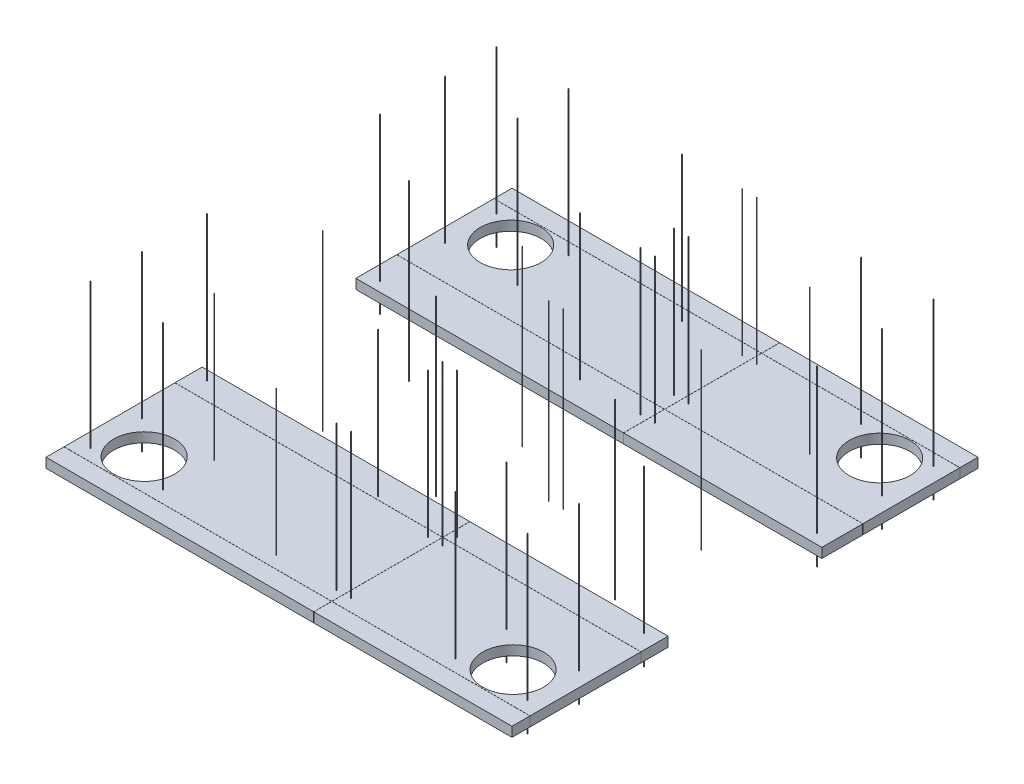
SolidWorks part; units mm, degrees
ref_plane "Front" through (0, 0, 0) normal (0, 0, 1) x (1, 0, 0)
ref_plane "Top" through (0, 0, 0) normal (0, 1, 0) x (1, 0, 0)
ref_plane "Right" through (0, 0, 0) normal (1, 0, 0) x (0, 0, -1)
sketch "Sketch1" plane through (0, 0, 0) normal (0, 1, 0) x (1, 0, 0)
  line L1 (-2454.275, 2454.275) -> (2454.275, 2454.275)
  line L2 (-2454.275, 2454.275) -> (-2454.275, -2454.275)
  line L3 (-2454.275, -2454.275) -> (2454.275, -2454.275)
  line L4 (2454.275, 2454.275) -> (2454.275, -2454.275)
  line L5 (-2454.275, 2454.275) -> (2454.275, -2454.275) construction
  line L6 (-2454.275, -2454.275) -> (2454.275, 2454.275) construction
  point P0 (0, 0)
  dimension "D1" = 4908.55
  dimension "D2" = 4908.55
extrude "Boss-Extrude1" add sketch "Sketch1" along normal blind 101.6
sketch "Sketch2" plane through (0, 101.6, 0) normal (0, 1, 0) x (1, 0, 0)
  line L0 (-2454.275, 2454.275) -> (-2454.275, -2454.275) construction
  line L1 (2454.275, -809.625) -> (-2454.275, -809.625)
  line L2 (2454.275, -809.625) -> (2454.275, 809.625)
  line L3 (2454.275, 809.625) -> (-2454.275, 809.625)
  line L4 (-2454.275, -809.625) -> (-2454.275, 809.625)
  line L5 (2454.275, -809.625) -> (-2454.275, 809.625) construction
  line L6 (2454.275, 809.625) -> (-2454.275, -809.625) construction
  point P0 (0, 0)
  dimension "D1" = 1619.25
extrude "Cut-Extrude1" cut sketch "Sketch2" against normal through all
sketch "Sketch4" plane through (0, 101.6, 0) normal (0, 1, 0) x (1, 0, 0)
  line L0 (-2454.275, -2263.775) -> (2454.275, -2263.775)
  line L3 (-2454.275, -2454.275) -> (2454.275, -2454.275) construction
  line L4 (-2454.275, -1095.375) -> (2454.275, -1095.375)
  line L5 (-2454.275, -809.625) -> (-2454.275, -2454.275) construction
  line L6 (-2454.275, -809.625) -> (2454.275, -809.625) construction
  line L7 (-2454.275, 2263.775) -> (2454.275, 2263.775)
  line L10 (-2454.275, 1241.425) -> (2454.275, 1241.425)
  line L11 (-2454.275, 2454.275) -> (-2454.275, 809.625) construction
  line L12 (2454.275, 809.625) -> (2454.275, 2454.275) construction
  line L13 (2454.275, 2454.275) -> (-2454.275, 2454.275) construction
  line L14 (2454.275, 809.625) -> (-2454.275, 809.625) construction
  line L15 (-2454.275, -1095.375) -> (-2454.275, -2263.775) construction
  line L16 (2454.275, -1095.375) -> (2454.275, -2263.775) construction
  line L17 (2454.275, 1241.425) -> (2454.275, 2263.775) construction
  line L18 (-2454.275, 1241.425) -> (-2454.275, 2263.775) construction
  line L19 (2454.275, -2454.275) -> (2454.275, -809.625) construction
  dimension "D1" = 190.5
  dimension "D2" = 1168.4
  dimension "D3" = 285.75
  dimension "D4" = 190.5
  dimension "D5" = 1022.35
  dimension "D6" = 431.8
extrude "Cut-Extrude-Thin1" cut sketch "Sketch4" against normal through all thin thin type one direction wall 1.27
sketch "Sketch5" plane through (0, 101.6, 0) normal (0, 1, 0) x (1, 0, 0)
  line L0 (365.125, -2454.275) -> (365.125, 2454.275)
  line L1 (-2454.275, -2454.275) -> (2454.275, -2454.275) construction
  line L2 (2454.275, 2454.275) -> (-2454.275, 2454.275) construction
  line L3 (2454.275, -2263.775) -> (2454.275, -1096.645) construction
  line L4 (-2454.275, -1096.645) -> (-2454.275, -2263.775) construction
  dimension "D1" = 2089.15
  dimension "D2" = 2819.4
extrude "Cut-Extrude-Thin2" cut sketch "Sketch5" against normal through all and the other way through all thin thin type one direction wall 1.27
sketch "Sketch8" plane through (0, 101.6, 0) normal (0, 1, 0) x (1, 0, 0)
  line L0 (-974.0807, 502.3386) -> (-974.0807, 1597.0052) construction
sketch "Sketch6" plane through (0, 101.6, 0) normal (0, 1, 0) x (1, 0, 0)
  line L0 (1943.1, 1929.13) -> (1943.1, 2262.505) construction
  line L1 (-1943.1, 1929.13) -> (1943.1, 1929.13) construction
  line L2 (-1943.1, 1929.13) -> (-1943.1, -1931.67) construction
  line L3 (-1943.1, -1931.67) -> (1943.1, -1931.67) construction
  line L4 (1943.1, 1929.13) -> (1943.1, -1931.67) construction
  line L5 (-1943.1, -1931.67) -> (-1943.1, -2265.045) construction
  line L6 (-2454.275, -2265.045) -> (365.125, -2265.045) construction
  line L7 (366.395, 2262.505) -> (2454.275, 2262.505) construction
  line L9 (2454.275, 1241.425) -> (2454.275, 2262.505) construction
  line L11 (-2454.275, -1096.645) -> (-2454.275, -2263.775) construction
  circle A0 centre (1943.1, 1929.13) radius 320.675
  circle A1 centre (-1943.1, 1929.13) radius 320.675
  circle A2 centre (-1943.1, -1931.67) radius 320.675
  circle A3 centre (1943.1, -1931.67) radius 320.675
  dimension "D1" = 641.35
  dimension "D3" = 190.5
  dimension "D4" = 190.5
  dimension "D2" = 12.7
extrude "DUCT HOLES" cut sketch "Sketch6" against normal through all
sketch "Sketch7" plane through (0, 101.6, 0) normal (0, 1, 0) x (1, 0, 0)
  line L0 (-1539.875, 2301.875) -> (-346.075, 2301.875) construction
  line L1 (-1539.875, 2301.875) -> (-2454.275, 2301.875) construction
  line L2 (-2454.275, 2454.275) -> (-2454.275, 2263.775) construction
  line L3 (365.125, 2454.275) -> (-2454.275, 2454.275) construction
  line L4 (-346.075, 2301.875) -> (365.125, 2301.875) construction
  line L5 (365.125, 2263.775) -> (365.125, 2454.275) construction
  line L6 (1539.875, 1597.025) -> (1539.875, 1063.625) construction
  line L7 (365.125, 2301.875) -> (974.725, 2301.875) construction
  line L8 (974.725, 2301.875) -> (1539.875, 2301.875) construction
  line L9 (1539.875, 2301.875) -> (2454.275, 2301.875) construction
  line L10 (2454.275, 2263.775) -> (2454.275, 2454.275) construction
  line L11 (366.395, 2263.775) -> (366.395, 2454.275) construction
  line L12 (2454.275, 1597.025) -> (-2454.275, 1597.025) construction
  line L13 (2454.275, 1241.425) -> (2454.275, 2262.505) construction
  line L14 (-2454.275, 2262.505) -> (-2454.275, 1241.425) construction
  line L15 (1539.875, 2301.875) -> (1539.875, 1597.025) construction
  line L16 (-2454.275, 1241.425) -> (365.125, 1241.425) construction
  line L17 (-346.075, 2301.875) -> (-346.075, 1597.025) construction
  line L18 (974.725, 2301.875) -> (974.725, 1597.025) construction
  line L19 (-2454.275, 2136.775) -> (2454.275, 2136.775) construction
  line L20 (-2454.275, 2263.775) -> (365.125, 2263.775) construction
  line L21 (-1539.875, 2301.875) -> (-1539.875, 2136.775) construction
  line L22 (-2454.275, 1063.625) -> (2454.275, 1063.625) construction
  line L23 (-2454.275, 1240.155) -> (-2454.275, 809.625) construction
  line L24 (2454.275, 809.625) -> (2454.275, 1240.155) construction
  line L25 (365.125, 809.625) -> (-2454.275, 809.625) construction
  line L26 (-1539.875, 1063.625) -> (-1539.875, 1597.025) construction
  line L27 (-346.075, 1597.025) -> (-346.075, 1063.625) construction
  line L28 (-2107.4102, -2022.1425) -> (-2107.4102, -819.4758) construction
  line L29 (-1539.875, 1285.875) -> (1539.875, 1285.875) construction
  line L30 (-2301.875, 1597.025) -> (-2301.875, 1063.625) construction
  line L31 (2301.875, 1597.025) -> (2301.875, 1063.625) construction
  line L32 (-2454.275, 1240.155) -> (365.125, 1240.155) construction
  line L33 (441.325, 1063.625) -> (288.925, 1063.625) construction
  line L34 (441.325, 1063.625) -> (441.325, 1416.685) construction
  line L35 (441.325, 1416.685) -> (288.925, 1416.685) construction
  line L36 (288.925, 1063.625) -> (288.925, 1416.685) construction
  line L37 (-2454.275, 1240.155) -> (365.125, 1240.155) construction
  line L38 (365.125, 809.625) -> (365.125, 1240.155) construction
  line L39 (365.125, 809.625) -> (365.125, 1240.155) construction
  line L40 (440.6472, 1241.425) -> (440.6472, 1063.625) construction
  line L41 (288.925, -1172.845) -> (441.325, -1172.845) construction
  line L42 (288.925, -1172.845) -> (288.925, -1020.445) construction
  line L43 (288.925, -1020.445) -> (441.325, -1020.445) construction
  line L44 (441.325, -1172.845) -> (441.325, -1020.445) construction
  line L45 (366.395, 1241.425) -> (2454.275, 1241.425) construction
  line L46 (1539.875, 1063.625) -> (1539.875, -2454.275) construction
  line L47 (366.395, -2454.275) -> (2454.275, -2454.275) construction
  line L48 (-2454.275, -1096.645) -> (365.125, -1096.645) construction
  line L49 (-2454.275, -1096.645) -> (365.125, -1096.645) construction
  line L50 (-2301.875, 1063.625) -> (-2301.875, 911.225) construction
  line L51 (-2301.875, 911.225) -> (2301.875, 911.225) construction
  line L52 (2301.875, 911.225) -> (2301.875, 1063.625) construction
  line L53 (-1539.875, 1063.625) -> (-1539.875, -2454.275) construction
  line L54 (-2454.275, -2454.275) -> (365.125, -2454.275) construction
  line L55 (1539.875, 454.025) -> (-1539.875, 454.025) construction
  line L56 (288.925, 1063.625) -> (288.925, -2454.275) construction
  line L57 (441.325, 1063.625) -> (441.325, -2454.275) construction
  line L58 (-346.075, 1063.625) -> (-346.075, -2454.275) construction
  line L59 (441.325, 98.425) -> (288.925, 98.425) construction
  line L60 (441.325, 1063.625) -> (441.325, 2301.875) construction
  line L61 (288.925, 1063.625) -> (288.925, 2301.875) construction
  circle A0 centre (-1539.875, 2301.875) radius 3.175 construction
  circle A4 centre (1539.875, 1597.025) radius 3.175
  circle A5 centre (-1539.875, 1597.025) radius 3.175
  circle A6 centre (441.325, 1063.625) radius 3.175
  circle A7 centre (-346.075, 1597.025) radius 3.175 construction
  circle A8 centre (974.725, 1597.025) radius 3.175 construction
  circle A9 centre (-346.075, 2136.775) radius 3.175
  circle A10 centre (-1539.875, 2136.775) radius 3.175
  circle A11 centre (974.725, 2136.775) radius 3.175 construction
  circle A12 centre (1539.875, 2136.775) radius 3.175
  circle A13 centre (-346.075, 1063.625) radius 3.175
  circle A14 centre (-1539.875, 1063.625) radius 3.175 construction
  circle A15 centre (1539.875, 1063.625) radius 3.175 construction
  circle A16 centre (-2301.875, 1597.025) radius 3.175
  circle A17 centre (2301.875, 1597.025) radius 3.175
  circle A18 centre (-2301.875, 2136.775) radius 3.175
  circle A19 centre (2301.875, 2136.775) radius 3.175
  circle A20 centre (219.075, 2301.875) radius 3.175 construction
  circle A21 centre (658.495, 2301.875) radius 3.175 construction
  circle A22 centre (1539.875, 2301.875) radius 3.175 construction
  circle A23 centre (-650.875, 2301.875) radius 3.175 construction
  circle A24 centre (-1539.875, 1285.875) radius 3.175 construction
  circle A25 centre (1539.875, 1285.875) radius 3.175 construction
  circle A26 centre (-2301.875, 1063.625) radius 3.175 construction
  circle A27 centre (2301.875, 1063.625) radius 3.175 construction
  circle A28 centre (288.925, 1416.685) radius 3.175
  circle A29 centre (441.325, 1416.685) radius 3.175
  circle A30 centre (288.925, 1063.625) radius 3.175
  circle A31 centre (441.325, -1020.445) radius 3.175
  circle A32 centre (288.925, -1020.445) radius 3.175
  circle A33 centre (288.925, -1172.845) radius 3.175
  circle A34 centre (441.325, -1172.845) radius 3.175
  circle A35 centre (-2301.875, 911.225) radius 3.175
  circle A36 centre (2301.875, 911.225) radius 3.175
  circle A37 centre (1539.875, 454.025) radius 3.175
  circle A38 centre (-1539.875, 454.025) radius 3.175
  circle A41 centre (-346.075, 454.025) radius 3.175
  circle A43 centre (441.325, 98.425) radius 3.175
  circle A44 centre (288.925, 98.425) radius 3.175
  circle A45 centre (288.925, 2136.775) radius 3.175
  circle A47 centre (441.325, 2136.775) radius 3.175
  point P107 (288.925, -1096.645)
  dimension "D1" = 6.35
  dimension "D5" = 609.6
  dimension "D7" = 355.6
  dimension "D11" = 152.4
  dimension "D14" = 152.4
  dimension "D19" = 889
  dimension "D20" = 914.4
  dimension "D21" = 1168.4
  dimension "D25" = 457.2
  dimension "D26" = 355.6
  dimension "D2" = 152.4
  dimension "D3" = 914.4
  dimension "D4" = 711.2
  dimension "D6" = 914.4
  dimension "D8" = 914.4
  dimension "D9" = 127
  dimension "D10" = 152.4
  dimension "D12" = 254
  dimension "D13" = 152.4
  dimension "D15" = 152.4
  dimension "D16" = 146.05
  dimension "D17" = 292.1
  dimension "D18" = 914.4
  dimension "D22" = 3079.75
  dimension "D23" = 152.4
  dimension "D24" = 152.4
extrude "UNISTRUT STUD LAYOUT" add sketch "Sketch7" along normal blind 1524 and the other way blind 304.8 separate body
mirror "Mirror3" about plane through (0, 0, 0) normal (0, 0, 1) of bodies 251 238 222 252 271 272 286 302 301 306 309 305 316 315 317 320 321 240 223 227 214 225 241 215 226 224 228 217 244 229 216 275 276 277 281 283 287 288 293 291
